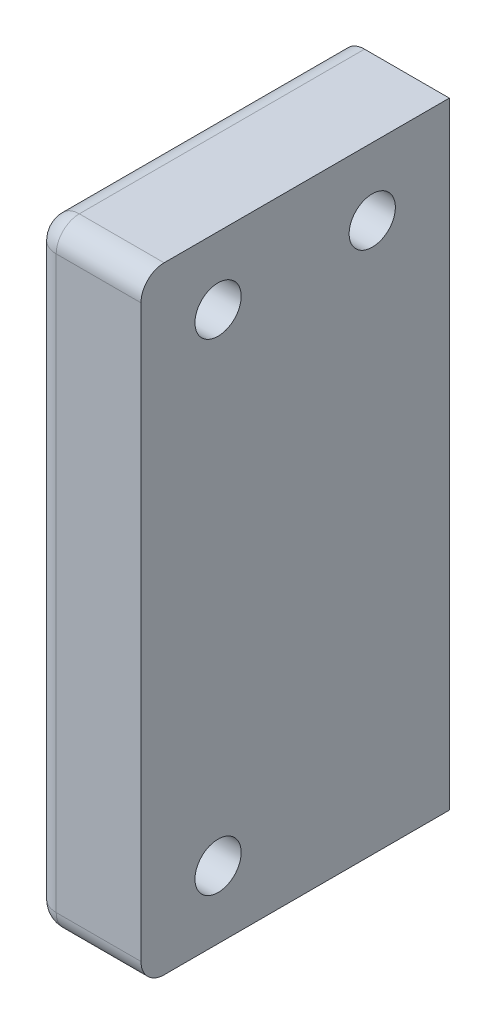
SolidWorks part; units mm, degrees
ref_plane "Front Plane" through (0, 0, 0) normal (0, 0, 1) x (1, 0, 0)
ref_plane "Top Plane" through (0, 0, 0) normal (0, 1, 0) x (1, 0, 0)
ref_plane "Right Plane" through (0, 0, 0) normal (1, 0, 0) x (0, 0, -1)
sketch "Sketch2" plane through (0, 0, 0) normal (0, 0, 1) x (1, 0, 0)
  line L0 (-148, -68) -> (-132, -68) construction
  line L1 (-148, -28) -> (-155, -28)
  line L2 (-148, -28) -> (-148, -68)
  line L3 (-148, -68) -> (-155, -68)
  line L4 (-155, -28) -> (-155, -68)
  point P1 (-155, -68)
  point P3 (-155.065, -28)
  point P4 (-155, -67.8782)
  point P5 (-154.9087, -28)
  point P9 (-155, -28)
  point P10 (-155, -68)
  point P13 (-154.9946, -28)
extrude "Boss-Extrude1" add sketch "Sketch2" along normal up to surface (20 mm away)
sketch "Sketch3" plane through (-148, 0, 0) normal (1, 0, 0) x (0, 0, -1)
  circle A0 centre (-15, -63.625) radius 1.5
  circle A2 centre (-5, -32.375) radius 1.5
  circle A3 centre (-15, -32.375) radius 1.5
extrude "Cut-Extrude1" cut sketch "Sketch3" against normal blind 10
fillet "Fillet1" radius 1.5 5 edges at (-151.5, -68, 20) (-151.5, -28, 20) (-155, -48, 20) (-155, -68, 10) (-155, -28, 10)
